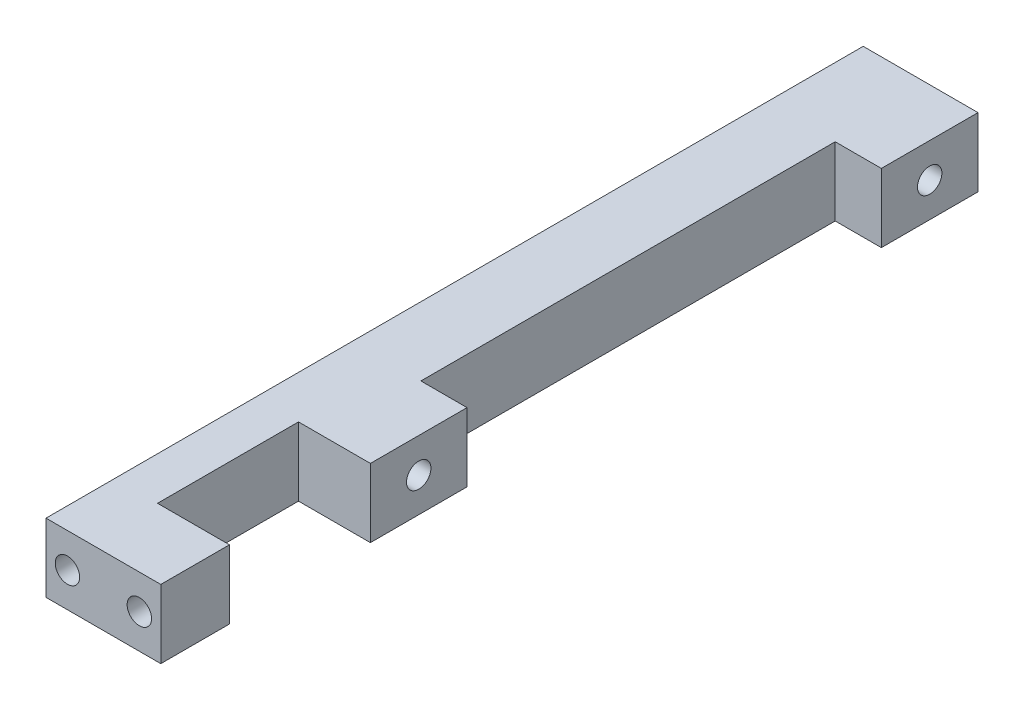
SolidWorks part; units mm, degrees
ref_plane "Front" through (0, 0, 0) normal (0, 0, 1) x (1, 0, 0)
ref_plane "Top" through (0, 0, 0) normal (0, 1, 0) x (1, 0, 0)
ref_plane "Right" through (0, 0, 0) normal (1, 0, 0) x (0, 0, -1)
sketch "Sketch1" plane through (0, 0, 0) normal (0, 1, 0) x (1, 0, 0)
  line L1 (-5.31, 37.8006) -> (5.31, 37.8006)
  line L2 (-5.31, 37.8006) -> (-5.31, -37.8006)
  line L3 (-5.31, -37.8006) -> (5.31, -37.8006)
  line L4 (5.31, 37.8006) -> (5.31, -37.8006)
  line L5 (-5.31, 37.8006) -> (5.31, -37.8006) construction
  line L6 (-5.31, -37.8006) -> (5.31, 37.8006) construction
  point P0 (0, 0)
  dimension "D1" = 75.6012
  dimension "D2" = 10.62
extrude "Boss-Extrude1" add sketch "Sketch1" along normal blind 6.35
hole_wizard "#4-40 Tapped Hole1" positions "Sketch3" profile "Sketch4" tap size "#4-40" standard "ANSI Inch"
sketch "Sketch3" plane through (5.31, 0, 0) normal (1, 0, 0) x (0, 0, -1)
  line L0 (33.3302, 3.175) -> (-13.9392, 3.175)
  line L2 (37.8006, 6.35) -> (37.8006, 0) construction
  line L3 (37.8006, 6.35) -> (33.3302, 3.175)
  line L6 (33.3302, 3.175) -> (37.8006, 0)
  point P0 (33.3302, 3.175)
  point P2 (-13.9392, 3.175)
  dimension "D1" = 47.2694
  dimension "D2" = 4.4704
cosmetic thread "Hole Thread1" parameters "D1"=6.096, "D2"=2.8448
cosmetic thread "Hole Thread2" parameters "D1"=6.096, "D2"=2.8448
sketch "Sketch4" plane through (5.31, 3.175, -33.3302) normal (0, 1, 0) x (0, 0, -1)
  line L0 (0, 0) -> (0, 7.0292)
  line L1 (0, 7.0292) -> (1.1303, 6.35)
  line L2 (1.1303, 6.35) -> (1.1303, 0)
  line L5 (1.1303, 0) -> (0, 0)
  line L10 (0, 7.0292) -> (-1.1303, 6.35) construction
  line L11 (0, -6.35) -> (0, 107.95) construction
  dimension "Tap Drill Dia." = 2.2606
  dimension "Tap Drill Depth" = 6.35
  dimension "Drill Angle" = 118
sketch "Sketch2" plane through (0, 6.35, 0) normal (0, 1, 0) x (1, 0, 0)
  line L0 (5.31, -37.8006) -> (5.31, 37.8006) construction
  line L1 (1.04, 28.8598) -> (5.31, 28.8598)
  line L2 (1.04, 28.8598) -> (1.04, -9.4688)
  line L3 (1.04, -9.4688) -> (5.31, -9.4688)
  line L4 (5.31, 28.8598) -> (5.31, -9.4688)
  line L5 (1.04, 28.8598) -> (5.31, -9.4688) construction
  line L6 (1.04, -9.4688) -> (5.31, 28.8598) construction
  line L7 (5.31, 32.1999) -> (5.31, 34.4605) construction
  line L8 (-1.3413, -31.4506) -> (5.31, -31.4506)
  line L9 (-1.3413, -31.4506) -> (-1.3413, -18.4096)
  line L10 (-1.3413, -18.4096) -> (5.31, -18.4096)
  line L11 (5.31, -31.4506) -> (5.31, -18.4096)
  line L12 (-1.3413, -31.4506) -> (5.31, -18.4096) construction
  line L13 (-1.3413, -18.4096) -> (5.31, -31.4506) construction
  line L14 (5.31, 32.1999) -> (5.31, 34.4605) construction
  line L15 (5.31, 34.4605) -> (5.31, 37.8006) construction
  line L16 (5.31, 32.1999) -> (5.31, 28.8598) construction
  line L17 (5.31, 32.1999) -> (5.31, 34.4605) construction
  line L19 (5.31, -15.0695) -> (5.31, -12.8089) construction
  line L20 (5.31, -15.0695) -> (5.31, -12.8089) construction
  line L21 (5.31, -12.8089) -> (5.31, -9.4688) construction
  line L22 (5.31, -15.0695) -> (5.31, -18.4096) construction
  line L23 (-5.31, 37.8006) -> (-5.31, -37.8006) construction
  line L24 (-5.31, -37.8006) -> (5.31, -37.8006) construction
  point P0 (3.175, 9.6955)
  point P8 (1.9844, -24.9301)
  dimension "D1" = 6.35
  dimension "D2" = 3.9688
  dimension "D3" = 6.35
extrude "Cut-Extrude1" cut sketch "Sketch2" against normal through all
hole_wizard "#4-40 Tapped Hole2" positions "Sketch5" profile "Sketch7" tap size "#4-40" standard "ANSI Inch"
sketch "Sketch5" plane through (0, 0, 37.8006) normal (0, 0, 1) x (1, 0, 0)
  line L0 (-5.31, 6.35) -> (-3.3256, 3.175) construction
  line L1 (-3.3256, 3.175) -> (3.3256, 3.175) construction
  line L2 (3.3256, 3.175) -> (5.31, 6.35) construction
  line L4 (3.3256, 3.175) -> (5.31, 0) construction
  line L5 (-3.3256, 3.175) -> (-1.3413, 6.35) construction
  point P0 (-3.3256, 3.175)
  point P2 (3.3256, 3.175)
sketch "Sketch7" plane through (-3.3256, 3.175, 37.8006) normal (1, 0, 0) x (0, -1, 0)
  line L0 (0, 0) -> (0, 8.2992)
  line L1 (0, 8.2992) -> (1.1303, 7.62)
  line L2 (1.1303, 7.62) -> (1.1303, 0)
  line L5 (1.1303, 0) -> (0, 0)
  line L10 (0, 8.2992) -> (-1.1303, 7.62) construction
  line L11 (0, -6.35) -> (0, 107.95) construction
  dimension "Tap Drill Dia." = 2.2606
  dimension "Tap Drill Depth" = 7.62
  dimension "Drill Angle" = 118
cosmetic thread "Hole Thread3" parameters "D1"=6.35, "D2"=2.8448
cosmetic thread "Hole Thread4" parameters "D1"=7.112, "D2"=2.8448
